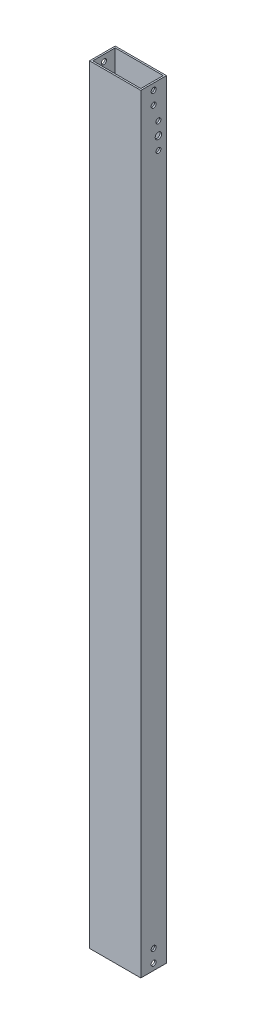
SolidWorks part; units mm, degrees
ref_plane "Front Plane" through (0, 0, 0) normal (0, 0, 1) x (1, 0, 0)
ref_plane "Top Plane" through (0, 0, 0) normal (0, 1, 0) x (1, 0, 0)
ref_plane "Right Plane" through (0, 0, 0) normal (1, 0, 0) x (0, 0, -1)
sketch "Sketch1" plane through (0, 0, 0) normal (0, 0, 1) x (1, 0, 0)
  line L1 (-25.4, -381) -> (25.4, -381)
  line L2 (-25.4, -381) -> (-25.4, 381)
  line L3 (-25.4, 381) -> (25.4, 381)
  line L4 (25.4, -381) -> (25.4, 381)
  line L5 (-25.4, -381) -> (25.4, 381) construction
  line L6 (-25.4, 381) -> (25.4, -381) construction
  point P0 (0, 0)
  dimension "D1" = 50.8
  dimension "D2" = 762
extrude "Boss-Extrude1" add sketch "Sketch1" along normal mid plane 25.4
shell "Shell1" thickness 1.5875 removed face at (0, -381, 0) removed face at (0, 381, 0)
sketch "Sketch3" plane through (0, 0, 0) normal (1, 0, 0) x (0, 0, -1)
  line L0 (-12.7, -381) -> (12.7, -381) construction
  circle A0 centre (0, -374.65) radius 2.4892
  circle A1 centre (0, -361.95) radius 2.4892
  point P6 (0, -381)
  dimension "D1" = 4.9784
  dimension "D2" = 6.35
  dimension "D3" = 12.7
extrude "Cut-Extrude1" cut sketch "Sketch3" against normal through all both and the other way through all
sketch "Sketch4" plane through (0, 0, 0) normal (1, 0, 0) x (0, 0, -1)
  line L0 (12.7, 381) -> (12.7, -381) construction
  line L3 (-12.7, 381) -> (12.7, 381) construction
  circle A0 centre (4.7625, 333.375) radius 3.175
  circle A1 centre (4.7625, 346.075) radius 2.4892
  circle A2 centre (4.7625, 320.675) radius 2.4892
  dimension "D1" = 6.35
  dimension "D4" = 4.9784
  dimension "D2" = 7.9375
  dimension "D5" = 12.7
  dimension "D6" = 12.7
  dimension "D3" = 47.625
extrude "Cut-Extrude2" cut sketch "Sketch4" against normal through all both and the other way through all
mirror "Mirror1" about plane through (0, 0, 0) normal (0, 1, 0) of "Cut-Extrude1"
sketch "Sketch5" plane through (0, 0, 0) normal (0, 0, 1) x (1, 0, 0)
  line L1 (-15.875, 346.8687) -> (15.875, 346.8687)
  line L2 (-15.875, 346.8687) -> (-15.875, 319.8812)
  line L3 (-15.875, 319.8812) -> (15.875, 319.8812)
  line L4 (15.875, 346.8687) -> (15.875, 319.8812)
  line L6 (25.4, 381) -> (-25.4, 381) construction
  point P4 (-15.875, 333.375)
  point P7 (-13.4926, 346.8687)
  point P8 (0, 346.8687)
  point P9 (0, 381)
  dimension "D1" = 31.75
  dimension "D2" = 26.9875
  dimension "D3" = 47.625
extrude "Cut-Extrude3" cut sketch "Sketch5" against normal through all
fillet "Fillet1" radius 3.175 4 edges at (15.875, 346.8687, -11.9062) (15.875, 319.8812, -11.9062) (-15.875, 319.8812, -11.9062) (-15.875, 346.8687, -11.9062)
equation "\"D6@Sketch4\"=\"D5@Sketch4\""
